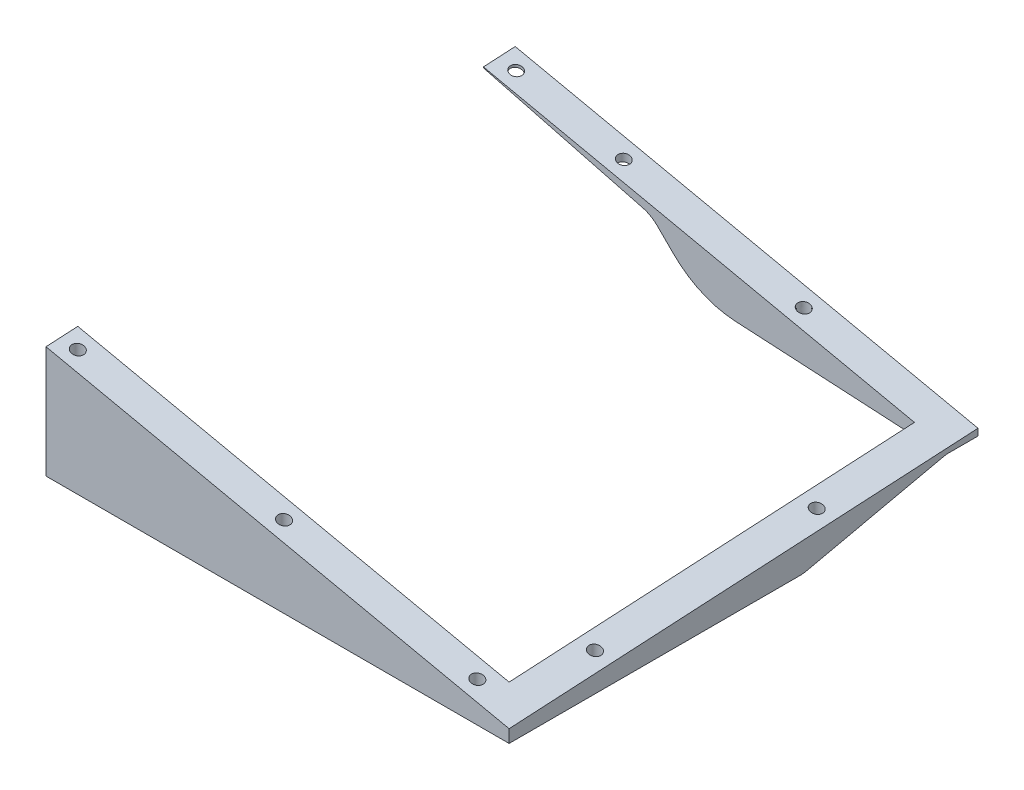
SolidWorks part; units mm, degrees
ref_plane "Front Plane" through (0, 0, 0) normal (0, 0, 1) x (1, 0, 0)
ref_plane "Top Plane" through (0, 0, 0) normal (0, 1, 0) x (1, 0, 0)
ref_plane "Right Plane" through (0, 0, 0) normal (1, 0, 0) x (0, 0, -1)
sketch "Sketch2" plane through (0, 0, 0) normal (0, 0, 1) x (1, 0, 0)
  line L0 (46.764, 18.415) -> (46.764, 20.32) construction
  line L1 (231.775, 18.415) -> (46.764, 18.415)
  line L2 (231.775, 18.415) -> (231.775, 88.415)
  line L3 (231.775, 88.415) -> (46.764, 88.415)
  line L4 (46.764, 18.415) -> (46.764, 88.415)
  dimension "D1" = 70
extrude "Boss-Extrude1" add sketch "Sketch2" against normal up to surface (12.7 mm away)
sketch "Sketch3" plane through (0, 0, -187.325) normal (0, 0, -1) x (-1, 0, 0)
  line L0 (-110.5935, 55.7937) -> (-46.891, 72.383) construction
  line L1 (-122.6856, 46.1714) -> (-116.3732, 52.4838) construction
  line L2 (-219.075, 31.115) -> (-147.5235, 35.0702) construction
  line L3 (-219.075, 31.115) -> (-231.775, 31.115) construction
  line L4 (-110.5935, 55.7937) -> (-46.891, 72.383)
  line L5 (-122.6856, 46.1714) -> (-116.3732, 52.4838)
  line L6 (-219.075, 31.115) -> (-147.5235, 35.0702)
  line L7 (-219.075, 31.115) -> (-231.775, 31.115)
  line L8 (-231.775, 88.415) -> (-231.775, 18.415) construction
  line L9 (-46.764, 88.415) -> (-231.775, 88.415) construction
  line L10 (-231.775, 88.415) -> (-231.775, 31.115)
  line L11 (-46.891, 88.415) -> (-231.775, 88.415)
  line L12 (-46.891, 88.415) -> (-46.891, 72.383)
  arc A0 (-110.5935, 55.7937) -> (-116.3732, 52.4838) centre (-107.3929, 43.5036) ccw construction
  arc A1 (-147.5235, 35.0702) -> (-122.6856, 46.1714) centre (-149.6264, 73.1121) ccw construction
  arc A2 (-110.5935, 55.7937) -> (-116.3732, 52.4838) centre (-107.3929, 43.5036) ccw
  arc A3 (-147.5235, 35.0702) -> (-122.6856, 46.1714) centre (-149.6264, 73.1121) ccw
extrude "Boss-Extrude2" add sketch "Sketch3" against normal up to surface (12.7 mm away) separate body
sketch "Sketch4" plane through (231.775, 0, 0) normal (1, 0, 0) x (0, 0, -1)
  line L0 (12.7, 88.415) -> (174.625, 88.415)
  line L1 (174.625, 88.415) -> (174.63, 31.0695)
  line L2 (174.63, 31.0695) -> (173.8085, 30.9335)
  line L3 (118.2915, 18.5965) -> (116.6385, 18.415)
  line L4 (116.6385, 18.415) -> (12.7, 18.415)
  line L5 (12.7, 18.415) -> (12.7, 88.415)
  line L6 (173.8085, 30.9335) -> (118.2915, 18.5965)
  arc A0 (175.4615, 31.115) -> (173.8085, 30.9335) centre (175.4615, 23.495) ccw construction
extrude "Boss-Extrude3" add sketch "Sketch4" against normal up to surface (12.7 mm away)
sketch "Sketch5" plane through (0, 0, -187.325) normal (0, 0, -1) x (-1, 0, 0)
  line L0 (-231.775, 88.415) -> (-46.764, 88.415)
  line L1 (-53.114, 215.9124) -> (-53.114, -14.5253) construction
  line L2 (-46.891, 88.415) -> (-231.775, 88.415) construction
  line L3 (-46.764, 88.415) -> (-46.764, 75.7624)
  line L4 (-46.764, 75.7624) -> (-231.775, 36.115)
  line L5 (-231.775, 88.415) -> (-231.775, 31.115) construction
  line L6 (-231.775, 36.115) -> (-231.775, 88.415)
  line L7 (-110.5935, 55.7937) -> (-46.891, 72.383) construction
  line L8 (-231.775, 31.115) -> (-219.075, 31.115) construction
  line L9 (-46.764, -13.2198) -> (-46.764, 214.3125) construction
  point P13 (-53.114, 70.7624)
  dimension "D1" = 5
  dimension "D2" = 5
extrude "Cut-Extrude1" cut sketch "Sketch5" against normal through all
ref_plane "Plane1" through (217.8254, -46.6794, 0) normal (0.9778, -0.2095, 0) x (0, 0, 1)
sketch "Sketch8" plane through (217.8254, -46.6794, 0) normal (0.9778, -0.2095, 0) x (0, 0, 1)
  line L0 (-187.325, -81.6321) -> (0, -71.5723)
  line L1 (0, -71.5723) -> (0, -83.8794)
  line L3 (-187.325, -81.6321) -> (-187.325, -83.8794)
  line L4 (-187.325, -83.8794) -> (0, -83.8794)
  line L5 (-12.7, -66.5723) -> (0, -66.5723) construction
  line L6 (0, -83.8794) -> (-187.325, -83.8794) construction
  line L7 (-187.325, -83.8794) -> (-187.325, -78.9904) construction
  dimension "D1" = 5
extrude "Cut-Extrude2" cut sketch "Sketch8" against normal through all
sketch "Sketch10" plane through (0, -35.385, 0) normal (0, -1, 0) x (1, 0, 0)
  circle A0 centre (53.114, -6.35) radius 2.413 construction
  circle A1 centre (135.523, -6.35) radius 2.413 construction
  circle A2 centre (212.725, -6.35) radius 2.413 construction
  circle A3 centre (225.425, -40.64) radius 2.413 construction
  circle A4 centre (53.114, -6.35) radius 2.413
  circle A5 centre (135.523, -6.35) radius 2.413
  circle A6 centre (212.725, -6.35) radius 2.413
  circle A7 centre (225.425, -40.64) radius 2.413
  ellipse E0 centre (168.5087, -180.975) end of major axis (168.5087, -183.388) minor radius 2.4093 construction
  ellipse E1 centre (53.6121, -180.975) end of major axis (53.6121, -183.388) minor radius 2.3351 construction
  ellipse E2 centre (96.6275, -180.975) end of major axis (96.6275, -183.388) minor radius 2.3351 construction
  ellipse E3 centre (225.425, -129.2375) end of major axis (227.5916, -130.2998) minor radius 2.3443 construction
  ellipse E4 centre (168.5087, -180.975) end of major axis (168.5087, -183.388) minor radius 2.4093
  ellipse E5 centre (53.6121, -180.975) end of major axis (53.6121, -183.388) minor radius 2.3351
  ellipse E6 centre (96.6275, -180.975) end of major axis (96.6275, -183.388) minor radius 2.3351
  ellipse E7 centre (225.425, -129.2375) end of major axis (227.5916, -130.2998) minor radius 2.3443
extrude "Cut-Extrude3" cut sketch "Sketch10" against normal through all
